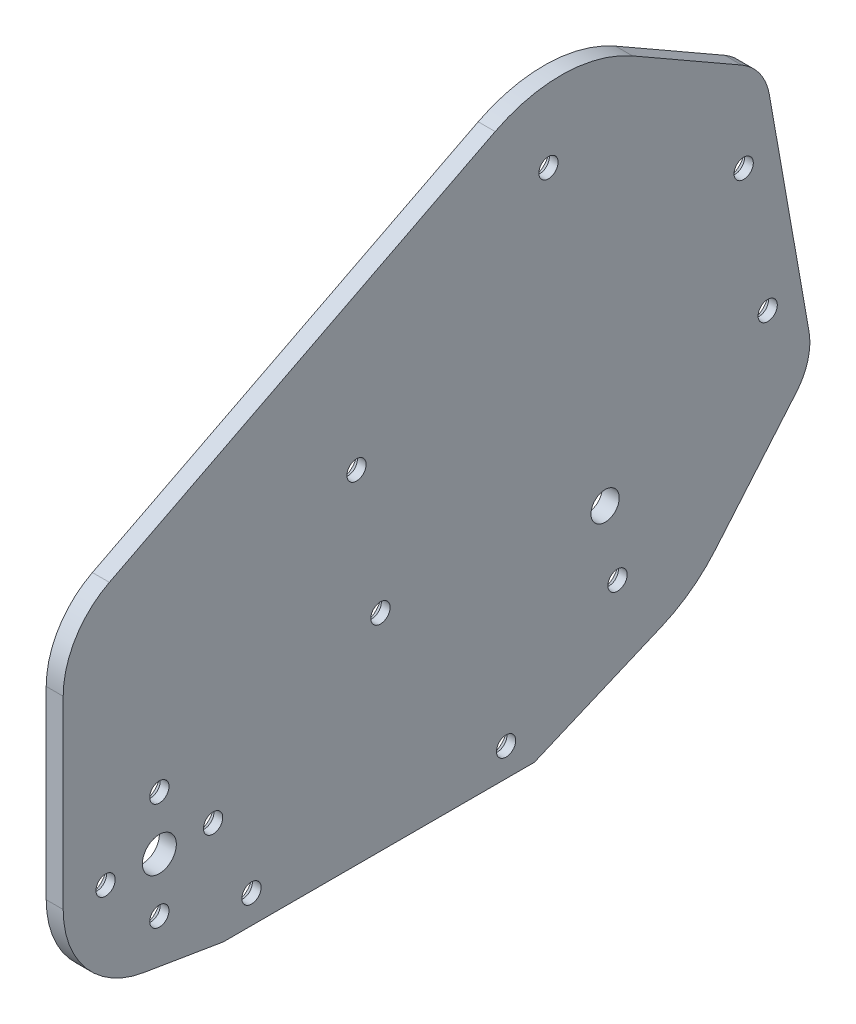
SolidWorks part; units mm, degrees
material "Thornel VCB-20 Carbon Cloth"
ref_plane "Front Plane" through (0, 0, 0) normal (0, 0, 1) x (1, 0, 0)
ref_plane "Top Plane" through (0, 0, 0) normal (0, 1, 0) x (1, 0, 0)
ref_plane "Right Plane" through (0, 0, 0) normal (1, 0, 0) x (0, 0, -1)
ref_plane "Plane1" through (-20, 0, 0) normal (-1, 0, 0) x (0, 0, 1)
sketch "Sketch2" plane through (-20, 0, 0) normal (-1, 0, 0) x (0, 0, 1)
  line L21 (-20.5659, 137.0149) -> (47.6199, 102.109)
  line L33 (-73.8247, 70.5164) -> (-59.4754, 53.5392)
  line L34 (-69.0263, 118.4582) -> (-76.0353, 78.7081)
  line L35 (-44.8568, 136.4454) -> (-64.1472, 125.3998)
  line L36 (16.6915, 108.8163) -> (-16.6101, 134.5066)
  line L37 (43.3893, 103.529) -> (18.8773, 107.8511)
  line L38 (55.7846, 56.1081) -> (55.7846, 88.7569)
  line L39 (27.5, 37) -> (41.5712, 39.3381)
  line L40 (-27.5, 37) -> (27.5, 37)
  line L41 (-49.9564, 46.5241) -> (-27.5, 37)
  line L42 (-73.8247, 70.5164) -> (-59.4754, 53.5392)
  line L43 (-69.0263, 118.4582) -> (-76.0353, 78.7081)
  line L44 (-44.8568, 136.4454) -> (-64.1472, 125.3998)
  line L47 (55.7846, 56.1081) -> (55.7846, 88.7569)
  line L48 (27.5, 37) -> (41.5712, 39.3381)
  line L49 (-27.5, 37) -> (27.5, 37)
  line L50 (-49.9564, 46.5241) -> (-27.5, 37)
  arc A22 (-76.0353, 78.7081) -> (-73.8247, 70.5164) centre (-66.1872, 76.9716) ccw
  arc A23 (-64.1472, 125.3998) -> (-69.0263, 118.4582) centre (-59.1782, 116.7217) ccw
  arc A24 (-16.6101, 134.5066) -> (-44.8568, 136.4454) centre (-32.1858, 114.3163) ccw
  arc A25 (16.6915, 108.8163) -> (18.8773, 107.8511) centre (19.7456, 112.7751) ccw
  arc A26 (55.7846, 88.7569) -> (43.3893, 103.529) centre (40.7846, 88.7569) ccw
  arc A27 (41.5712, 39.3381) -> (55.7846, 56.1081) centre (38.7846, 56.1081) ccw
  arc A28 (-59.4754, 53.5392) -> (-49.9564, 46.5241) centre (-40, 70) ccw
  arc A29 (-76.0353, 78.7081) -> (-73.8247, 70.5164) centre (-66.1872, 76.9716) ccw
  arc A30 (-64.1472, 125.3998) -> (-69.0263, 118.4582) centre (-59.1782, 116.7217) ccw
  arc A31 (-20.5659, 137.0149) -> (-44.8568, 136.4454) centre (-32.1858, 114.3163) ccw
  arc A33 (55.7846, 88.7569) -> (47.6199, 102.109) centre (40.7846, 88.7569) ccw
  arc A34 (41.5712, 39.3381) -> (55.7846, 56.1081) centre (38.7846, 56.1081) ccw
  arc A35 (-59.4754, 53.5392) -> (-49.9564, 46.5241) centre (-40, 70) ccw
  dimension "D1" = 0
extrude "Boss-Extrude1" add sketch "Sketch2" along normal blind 3 contours L42 A35 L50 L49 L48 A34 L47 A33 L21 A31 L44 A30 L43 A29 region at (-20, 115.7187, 14.9406) region at (-20, 82.4064, -11.6288)
sketch "Sketch7" plane through (0, 0, 0) normal (1, 0, 0) x (0, 0, -1)
  line L1 (-38.7846, 65.6081) -> (-48.2846, 56.1081)
  line L2 (-48.2846, 56.1081) -> (-38.7846, 46.6081)
  line L3 (-38.7846, 46.6081) -> (-29.2846, 56.1081)
  line L4 (-29.2846, 56.1081) -> (-38.7846, 65.6081)
  circle A0 centre (-38.7846, 56.1081) radius 14 construction
  circle A1 centre (-38.7846, 56.1081) radius 14 construction
  circle A2 centre (-38.7846, 56.1081) radius 9.5 construction
  circle A3 centre (-38.7846, 56.1081) radius 6.7175 construction
  dimension "D1" = 19
hole_wizard "CSK for M3 Flat Head Machine Screw1" positions "Sketch3" profile "Sketch4" countersink size "M3" standard "ANSI Metric" end condition through all
sketch "Sketch3" plane through (-23, 0, 0) normal (-1, 0, 0) x (0, 0, 1)
  point P0 (-64.4907, 109.4197)
  point P2 (-68.7373, 85.5447)
  point P5 (-29.9892, 126.7742)
  point P8 (-42.1966, 57.5422)
  point P11 (-0.2931, 73.4761)
  point P14 (3.9375, 97.4693)
  point P17 (22.5, 42)
  point P20 (-22.5, 42)
  point P24 (38.7846, 65.6081)
  point P27 (48.2846, 56.1081)
  point P30 (38.7846, 46.6081)
  point P33 (29.2846, 56.1081)
sketch "Sketch4" plane through (-23, 109.4197, -64.4907) normal (0, 1, 0) x (0, 0, 1)
  line L0 (0, 0) -> (0, 3)
  line L1 (0, 3) -> (1.7, 3)
  line L2 (1.7, 3) -> (1.7, 1.45)
  line L3 (1.7, 1.45) -> (3.15, 0)
  line L5 (3.15, 0) -> (0, 0)
  line L6 (-1.7, 1.45) -> (-3.15, 0) construction
  line L11 (0, -6.35) -> (0, 107.95) construction
  dimension "Thru Hole Dia." = 3.4
  dimension "Thru Hole Depth" = 3
  dimension "Near C'Sink Dia." = 6.3
  dimension "Near C'Sink Angle" = 90
hole_wizard "Hole1" positions "Sketch5" profile "Sketch6" legacy end condition through all
sketch "Sketch5" plane through (-23, 0, 0) normal (-1, 0, 0) x (0, 0, 1)
  point P0 (-40, 70)
sketch "Sketch6" plane through (-23, 70, -40) normal (0, 1, 0) x (0, 0, 1)
  line L0 (0, 0) -> (0, 3)
  line L1 (0, 3) -> (2.5, 3)
  line L2 (2.5, 3) -> (2.5, 0)
  line L3 (2.5, 0) -> (0, 0)
  line L4 (0, 110) -> (0, -10) construction
  dimension "Diameter" = 5
  dimension "Depth" = 3
hole_wizard "Hole2" positions "Sketch8" profile "Sketch9" legacy end condition through all
sketch "Sketch8" plane through (-23, 0, 0) normal (-1, 0, 0) x (0, 0, 1)
  point P0 (38.7846, 56.1081)
sketch "Sketch9" plane through (-23, 56.1081, 38.7846) normal (0, 1, 0) x (0, 0, 1)
  line L0 (0, 0) -> (0, 3)
  line L1 (0, 3) -> (3, 3)
  line L2 (3, 3) -> (3, 0)
  line L3 (3, 0) -> (0, 0)
  line L4 (0, 110) -> (0, -10) construction
  dimension "Diameter" = 6
  dimension "Depth" = 3
